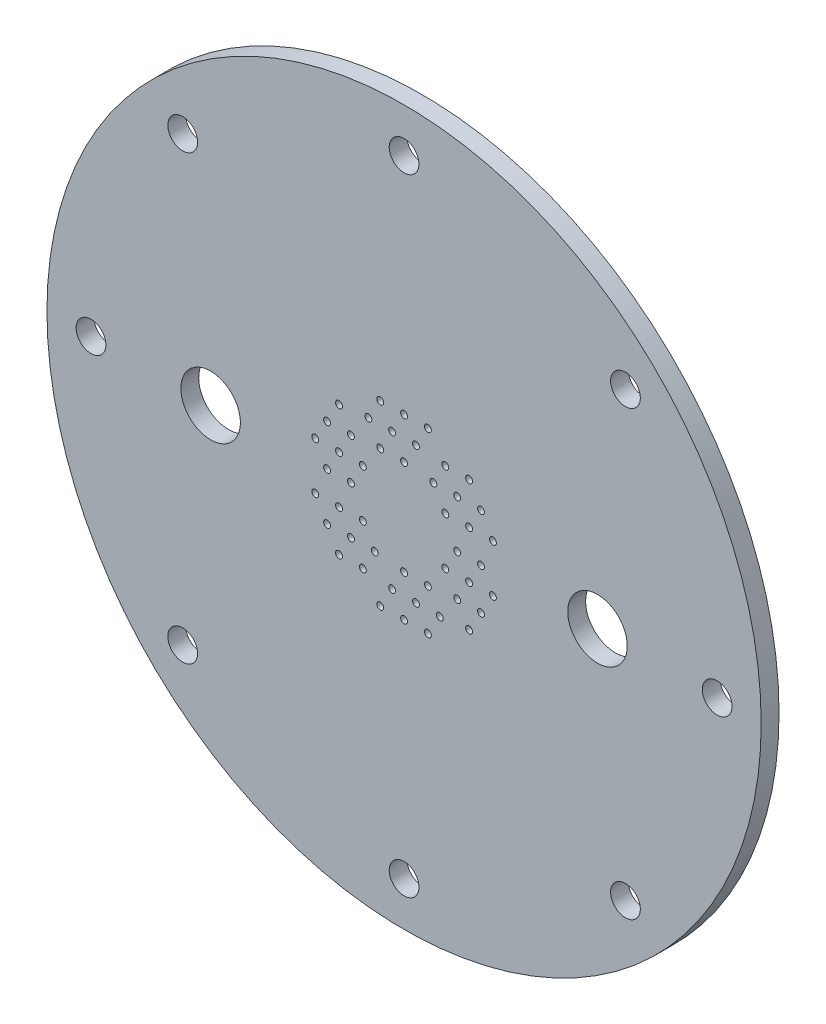
SolidWorks part; units mm, degrees
ref_plane "Front Plane" through (0, 0, 0) normal (0, 0, 1) x (1, 0, 0)
ref_plane "Top Plane" through (0, 0, 0) normal (0, 1, 0) x (1, 0, 0)
ref_plane "Right Plane" through (0, 0, 0) normal (1, 0, 0) x (0, 0, -1)
sketch "Sketch1" plane through (0, 0, 0) normal (0, 0, 1) x (1, 0, 0)
  circle A0 centre (0, 0) radius 76.2
  dimension "Top Injector Diameter" = 152.4
extrude "Boss-Extrude1" add sketch "Sketch1" along normal blind 3.81
sketch "Sketch2" plane through (0, 0, 0) normal (0, 0, -1) x (-1, 0, 0)
  line L0 (0, 0) -> (0, 10.16) construction
  line L1 (0, 10.16) -> (5.08, 10.16) construction
  line L2 (5.08, 10.16) -> (7.62, 14.5594) construction
  line L3 (7.62, 14.5594) -> (2.54, 14.5594) construction
  line L4 (2.54, 14.5594) -> (5.08, 10.16) construction
  line L5 (0, 10.16) -> (2.54, 14.5594) construction
  line L6 (0, 10.16) -> (-2.54, 14.5594) construction
  line L7 (-2.54, 14.5594) -> (2.54, 14.5594) construction
  line L8 (2.54, 14.5594) -> (5.08, 18.9588) construction
  line L9 (5.08, 18.9588) -> (7.62, 14.5594) construction
  line L10 (-2.54, 14.5594) -> (-5.08, 18.9588) construction
  line L11 (-5.08, 18.9588) -> (0, 18.9588) construction
  line L12 (0, 18.9588) -> (-2.54, 14.5594) construction
  line L13 (0, 18.9588) -> (2.54, 14.5594) construction
  line L14 (0, 18.9588) -> (5.08, 18.9588) construction
  circle A0 centre (0, 10.16) radius 0.7366
  circle A1 centre (2.54, 14.5594) radius 0.7366
  circle A2 centre (5.08, 10.16) radius 0.7366
  circle A3 centre (7.62, 14.5594) radius 0.7366
  circle A4 centre (-2.54, 14.5594) radius 0.7366
  circle A5 centre (-5.08, 18.9588) radius 0.7366
  circle A6 centre (0, 18.9588) radius 0.7366
  circle A7 centre (5.08, 18.9588) radius 0.7366
  dimension "Top Injector Hole Diameter" = 1.4732
  dimension "Distance Between Holes" = 5.08
  dimension "Top Injector Hole Distance from Center" = 10.16
extrude "Cut-Extrude1" cut sketch "Sketch2" against normal through all
pattern_circular "CirPattern1" count 6 over 360 about axis through (0, 0, 3.81) along (0, 0, -1) of "Cut-Extrude1"
sketch "Sketch3" plane through (0, 0, 0) normal (0, 0, -1) x (-1, 0, 0)
  line L0 (-41.275, 0) -> (41.275, 0) construction
  circle A0 centre (41.275, 0) radius 6.35
  circle A1 centre (-41.275, 0) radius 6.35
  point P4 (0, 0)
  dimension "Top Injector Valves Diameter" = 12.7
  dimension "Top Injector Manifold Valves" = 82.55
extrude "Cut-Extrude2" cut sketch "Sketch3" against normal through all
sketch "Sketch5" plane through (0, 0, 0) normal (0, 0, -1) x (-1, 0, 0)
  line L0 (0, 0) -> (66.802, 0) construction
  circle A0 centre (66.802, 0) radius 3.175
  dimension "Top Injector Hole Diameter" = 6.35
  dimension "Top Injector Screw Holes Distance" = 66.802
extrude "Cut-Extrude3" cut sketch "Sketch5" against normal through all
pattern_circular "CirPattern2" count 8 over 360 about axis through (0, 0, 3.81) along (0, 0, 1) of "Cut-Extrude3"
sketch "Sketch6" plane through (0, 0, 0) normal (1, 0, 0) x (0, 0, -1)
  line L0 (0, -76.2) -> (0, 76.2) construction
  line L1 (0, 53.34) -> (1.27, 53.34)
  line L2 (0, 53.34) -> (0, 50.8)
  line L3 (0, 50.8) -> (1.27, 50.8)
  line L4 (1.27, 53.34) -> (1.27, 50.8)
  line L5 (0, 76.2) -> (-3.81, 76.2) construction
  line L6 (0, 0) -> (-3.81, 0) construction
  line L7 (-3.81, 76.2) -> (-3.81, -76.2) construction
  dimension "Locator Ring Width" = 2.54
  dimension "Locator Ring Distance From Edge" = 25.4
  dimension "Locator Ring Depth" = 1.27
revolve "Revolve1" add sketch "Sketch6" angle 360 about L6
equation "\"Top Injector Diameter\"=6"
equation "\"Top Injector Height\"=0.15"
equation "\"Distance Between Holes\"=0.2"
equation "\"Top Injector Hole Distance from Center\"=0.4"
equation "\"Top Injector Hole Diameter\"=0.058"
equation "\"Top Injector Manifold Valves\"=3.25"
equation "\"Top Injector Valves Diameter\"=0.5"
equation "\"Top Injector Screw Holes Distance\"=2.63"
equation "\"Top Injector Screw Hole Diameter\"=0.25"
